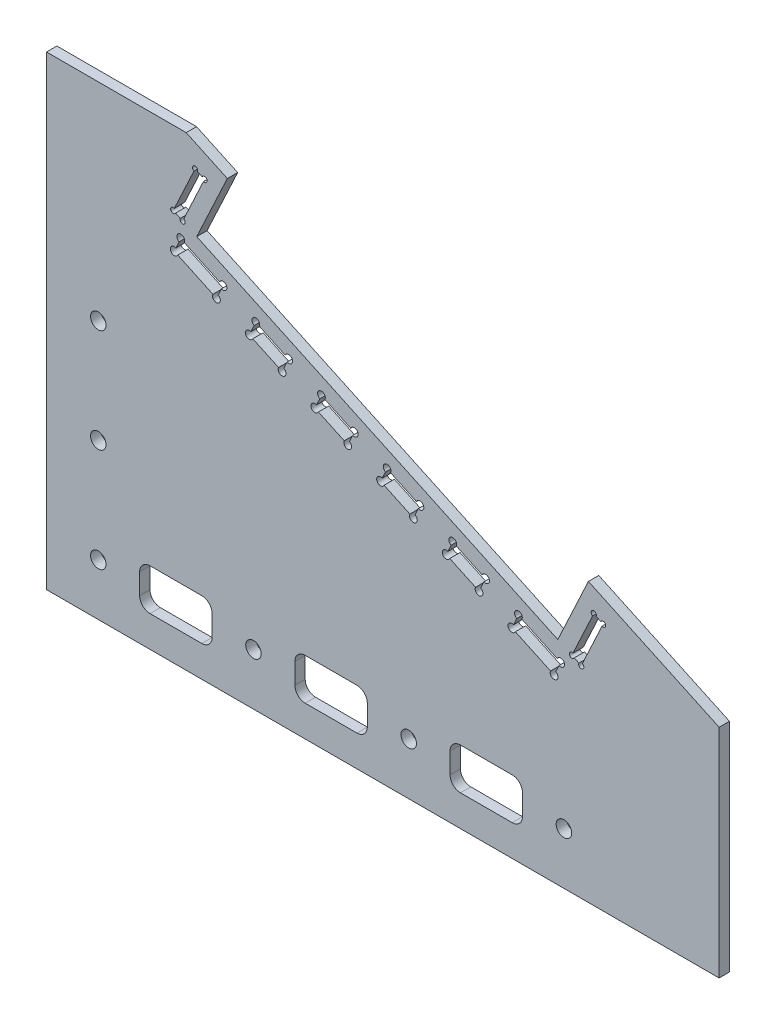
SolidWorks part; units mm, degrees
material "Thornel Mat VMA"
ref_plane "前视基准面" through (0, 0, 0) normal (0, 0, 1) x (1, 0, 0)
ref_plane "上视基准面" through (0, 0, 0) normal (0, 1, 0) x (1, 0, 0)
ref_plane "右视基准面" through (0, 0, 0) normal (1, 0, 0) x (0, 0, -1)
sketch "草图1" plane through (0, 0, 0) normal (0, 0, 1) x (1, 0, 0)
  line L1 (0, 0) -> (130, 0)
  line L2 (0, 0) -> (0, 90)
  line L3 (0, 90) -> (130, 90)
  line L4 (130, 0) -> (130, 90)
  circle A0 centre (10, 10) radius 1.5
  circle A1 centre (10, 30) radius 1.5
  circle A2 centre (10, 50) radius 1.5
  circle A3 centre (40, 10) radius 1.5
  circle A4 centre (70, 10) radius 1.5
  circle A5 centre (100, 10) radius 1.5
  dimension "D3" = 3
  dimension "D1" = 90
  dimension "D2" = 130
  dimension "D4" = 10
  dimension "D5" = 10
  dimension "D6" = 20
  dimension "D7" = 20
  dimension "D8" = 30
  dimension "D9" = 30
  dimension "D10" = 30
extrude "凸台-拉伸1" add sketch "草图1" along normal blind 2
sketch "草图2" plane through (0, 0, 2) normal (0, 0, 1) x (1, 0, 0)
  line L0 (27, 90) -> (130, 41.9703)
  line L1 (130, 90) -> (0, 90) construction
  line L2 (130, 0) -> (130, 90) construction
  line L3 (0, 90) -> (0, 0) construction
  line L4 (27, 90) -> (130, 90)
  line L5 (130, 90) -> (130, 41.9703)
  dimension "D1" = 27
  dimension "D2" = 25
extrude "切除-拉伸1" cut sketch "草图2" against normal through all
sketch "草图3" plane through (0, 0, 2) normal (0, 0, 1) x (1, 0, 0)
  line L0 (34.9483, 86.2936) -> (104.734, 53.752)
  line L1 (34.9483, 86.2936) -> (29.0317, 73.6053)
  line L2 (104.734, 53.752) -> (98.8174, 41.0637)
  line L3 (29.0317, 73.6053) -> (98.8174, 41.0637)
  line L4 (27, 90) -> (130, 41.9703) construction
  dimension "D1" = 14
  dimension "D2" = 77
  dimension "D3" = 8.77
extrude "切除-拉伸2" cut sketch "草图3" against normal through all
sketch "草图4" plane through (0, 0, 2) normal (0, 0, 1) x (1, 0, 0)
  line L0 (25.0449, 72.1543) -> (100.2684, 37.0769) construction
  line L1 (29.0317, 73.6053) -> (98.8174, 41.0637) construction
  line L2 (34.9483, 86.2936) -> (29.0317, 73.6053) construction
  line L3 (98.8174, 41.0637) -> (104.734, 53.752) construction
  line L4 (25.0449, 72.1543) -> (32.2294, 87.5615) construction
  line L5 (27, 90) -> (34.9483, 86.2936) construction
  line L6 (100.2684, 37.0769) -> (107.4529, 52.4842) construction
  line L7 (104.734, 53.752) -> (130, 41.9703) construction
  line L8 (30.5389, 83.9363) -> (26.3127, 74.8732)
  line L9 (30.5389, 83.9363) -> (28.7172, 84.7857)
  line L10 (26.3127, 74.8732) -> (24.4911, 75.7226)
  line L11 (28.7172, 84.7857) -> (24.4911, 75.7226)
  line L12 (105.7625, 48.8589) -> (101.5363, 39.7959)
  line L13 (105.7625, 48.8589) -> (107.5751, 48.0137)
  line L14 (101.5363, 39.7959) -> (103.3489, 38.9506)
  line L15 (107.5751, 48.0137) -> (103.3489, 38.9506)
  line L16 (25.9512, 71.7316) -> (34.108, 67.9281)
  line L17 (25.9512, 71.7316) -> (24.6833, 69.0127)
  line L18 (34.108, 67.9281) -> (32.8401, 65.2092)
  line L19 (24.6833, 69.0127) -> (32.8401, 65.2092)
  line L20 (40.4521, 64.9697) -> (46.7963, 62.0114)
  line L21 (40.4521, 64.9697) -> (39.1843, 62.2508)
  line L22 (46.7963, 62.0114) -> (45.5284, 59.2925)
  line L23 (39.1843, 62.2508) -> (45.5284, 59.2925)
  line L24 (78.517, 47.2198) -> (84.8612, 44.2615)
  line L25 (78.517, 47.2198) -> (77.2492, 44.5009)
  line L26 (84.8612, 44.2615) -> (83.5933, 41.5425)
  line L27 (77.2492, 44.5009) -> (83.5933, 41.5425)
  line L28 (91.2054, 41.3031) -> (99.3621, 37.4996)
  line L29 (91.2054, 41.3031) -> (89.9375, 38.5842)
  line L30 (99.3621, 37.4996) -> (98.0943, 34.7806)
  line L31 (89.9375, 38.5842) -> (98.0943, 34.7806)
  line L32 (53.1404, 59.0531) -> (59.4846, 56.0948)
  line L37 (53.1404, 59.0531) -> (51.8726, 56.3342)
  line L38 (59.4846, 56.0948) -> (58.2167, 53.3758)
  line L39 (51.8726, 56.3342) -> (58.2167, 53.3758)
  line L40 (65.8287, 53.1364) -> (72.1729, 50.1781)
  line L41 (65.8287, 53.1364) -> (64.5609, 50.4175)
  line L42 (72.1729, 50.1781) -> (70.905, 47.4592)
  line L43 (64.5609, 50.4175) -> (70.905, 47.4592)
  point P21 (25.3173, 70.3722)
  point P37 (33.474, 66.5686)
  dimension "D1" = 3
  dimension "D2" = 3
  dimension "D3" = 3
  dimension "D4" = 1
  dimension "D5" = 2
  dimension "D6" = 9
  dimension "D7" = 9
  dimension "D8" = 1.5
  dimension "D9" = 7
  dimension "D10" = 7
  dimension "D11" = 7
  dimension "D12" = 7
  dimension "D13" = 1
  dimension "D14" = 3
  dimension "D15" = 3
  dimension "D16" = 3
  dimension "D17" = 3
  dimension "D18" = 10
  dimension "D19" = 2.01
  dimension "D20" = 3
  dimension "D21" = 10
  dimension "D22" = 7
  dimension "D23" = 7
  dimension "D24" = 3
  dimension "D25" = 7
  dimension "D26" = 7
  dimension "D27" = 3
extrude "切除-拉伸3" cut sketch "草图4" against normal through all
sketch "草图5" plane through (0, 0, 2) normal (0, 0, 1) x (1, 0, 0)
  line L0 (114.7802, 44.6539) -> (110.554, 35.5908)
  line L1 (114.7802, 44.6539) -> (117.4992, 43.386)
  line L2 (110.554, 35.5908) -> (113.273, 34.323)
  line L3 (117.4992, 43.386) -> (113.273, 34.323)
  line L4 (101.5363, 39.7959) -> (103.3489, 38.9506) construction
  line L5 (103.3489, 38.9506) -> (107.5751, 48.0137) construction
  dimension "D1" = 7.95
  dimension "D2" = 3
  dimension "D3" = 10
extrude "切除-拉伸4" [suppressed] cut sketch "草图5" against normal through all
sketch "草图6" plane through (0, 0, 2) normal (0, 0, 1) x (1, 0, 0)
  circle A0 centre (24.6833, 69.0127) radius 0.75
  circle A1 centre (25.9512, 71.7316) radius 0.75
  circle A2 centre (34.108, 67.9281) radius 0.75
  circle A3 centre (32.8401, 65.2092) radius 0.75
  circle A4 centre (45.5284, 59.2925) radius 0.75
  circle A5 centre (39.1843, 62.2508) radius 0.75
  circle A6 centre (40.4521, 64.9697) radius 0.75
  circle A7 centre (46.7963, 62.0114) radius 0.75
  circle A8 centre (78.517, 47.2198) radius 0.75
  circle A9 centre (77.2492, 44.5009) radius 0.75
  circle A10 centre (83.5933, 41.5425) radius 0.75
  circle A11 centre (84.8612, 44.2615) radius 0.75
  circle A12 centre (98.0943, 34.7806) radius 0.75
  circle A13 centre (99.3621, 37.4996) radius 0.75
  circle A14 centre (91.2054, 41.3031) radius 0.75
  circle A15 centre (89.9375, 38.5842) radius 0.75
  circle A16 centre (26.3127, 74.8732) radius 0.5
  circle A17 centre (24.4911, 75.7226) radius 0.5
  circle A18 centre (28.7172, 84.7857) radius 0.5
  circle A19 centre (30.5389, 83.9363) radius 0.5
  circle A20 centre (103.3489, 38.9506) radius 0.5
  circle A21 centre (101.5363, 39.7959) radius 0.5
  circle A22 centre (105.7625, 48.8589) radius 0.5
  circle A23 centre (107.5751, 48.0137) radius 0.5
  circle A24 centre (53.1404, 59.0531) radius 0.75
  circle A25 centre (59.4846, 56.0948) radius 0.75
  circle A26 centre (51.8726, 56.3342) radius 0.75
  circle A27 centre (58.2167, 53.3758) radius 0.75
  circle A28 centre (65.8287, 53.1364) radius 0.75
  circle A29 centre (72.1729, 50.1781) radius 0.75
  circle A30 centre (70.905, 47.4592) radius 0.75
  circle A31 centre (64.5609, 50.4175) radius 0.75
  dimension "D1" = 1
  dimension "D2" = 1.5
  dimension "D3" = 1.5
  dimension "D4" = 1.5
  dimension "D5" = 1.5
  dimension "D6" = 1.5
  dimension "D7" = 1.5
  dimension "D8" = 1.5
  dimension "D9" = 1.5
  dimension "D10" = 1.5
extrude "切除-拉伸5" cut sketch "草图6" against normal blind 10
sketch "草图7" plane through (0, 0, 2) normal (0, 0, 1) x (1, 0, 0)
  line L0 (0, 20) -> (130, 20) construction
  line L1 (0, 90) -> (0, 0) construction
  line L2 (130, 0) -> (130, 41.9703) construction
  line L3 (0, 0) -> (130, 0) construction
  line L4 (130, 20) -> (112.6424, 50.0643)
  line L5 (104.734, 53.752) -> (130, 41.9703) construction
  line L6 (112.6424, 50.0643) -> (130, 41.9703)
  line L7 (130, 41.9703) -> (130, 20)
  dimension "D1" = 20
  dimension "D2" = 60
extrude "切除-拉伸6" [suppressed] cut sketch "草图7" against normal blind 10
fillet "圆角1" [suppressed] radius 2
sketch "草图8" plane through (0, 0, 0) normal (0, 0, -1) x (-1, 0, 0)
  line L0 (-90, 14) -> (-80, 14) construction
  line L1 (-92, 8) -> (-92, 12) construction
  line L2 (-80, 6) -> (-90, 6) construction
  line L3 (-78, 12) -> (-78, 8) construction
  line L4 (-62, 8) -> (-62, 12) construction
  line L5 (-50, 6) -> (-60, 6) construction
  line L6 (-60, 14) -> (-50, 14) construction
  line L7 (-48, 12) -> (-48, 8) construction
  line L8 (-30, 14) -> (-20, 14) construction
  line L9 (-32, 8) -> (-32, 12) construction
  line L10 (-20, 6) -> (-30, 6) construction
  line L11 (-18, 12) -> (-18, 8) construction
  line L12 (-90, 14) -> (-80, 14)
  line L13 (-92, 8) -> (-92, 12)
  line L14 (-80, 6) -> (-90, 6)
  line L15 (-78, 12) -> (-78, 8)
  line L16 (-62, 8) -> (-62, 12)
  line L17 (-50, 6) -> (-60, 6)
  line L18 (-60, 14) -> (-50, 14)
  line L19 (-48, 12) -> (-48, 8)
  line L20 (-30, 14) -> (-20, 14)
  line L21 (-32, 8) -> (-32, 12)
  line L22 (-20, 6) -> (-30, 6)
  line L23 (-18, 12) -> (-18, 8)
  arc A0 (-78, 12) -> (-80, 14) centre (-80, 12) ccw construction
  arc A1 (-90, 14) -> (-92, 12) centre (-90, 12) ccw construction
  arc A2 (-92, 8) -> (-90, 6) centre (-90, 8) ccw construction
  arc A3 (-80, 6) -> (-78, 8) centre (-80, 8) ccw construction
  arc A4 (-60, 14) -> (-62, 12) centre (-60, 12) ccw construction
  arc A5 (-62, 8) -> (-60, 6) centre (-60, 8) ccw construction
  arc A6 (-48, 12) -> (-50, 14) centre (-50, 12) ccw construction
  arc A7 (-50, 6) -> (-48, 8) centre (-50, 8) ccw construction
  arc A8 (-30, 14) -> (-32, 12) centre (-30, 12) ccw construction
  arc A9 (-32, 8) -> (-30, 6) centre (-30, 8) ccw construction
  arc A10 (-18, 12) -> (-20, 14) centre (-20, 12) ccw construction
  arc A11 (-20, 6) -> (-18, 8) centre (-20, 8) ccw construction
  arc A12 (-78, 12) -> (-80, 14) centre (-80, 12) ccw
  arc A13 (-90, 14) -> (-92, 12) centre (-90, 12) ccw
  arc A14 (-92, 8) -> (-90, 6) centre (-90, 8) ccw
  arc A15 (-80, 6) -> (-78, 8) centre (-80, 8) ccw
  arc A16 (-60, 14) -> (-62, 12) centre (-60, 12) ccw
  arc A17 (-62, 8) -> (-60, 6) centre (-60, 8) ccw
  arc A18 (-48, 12) -> (-50, 14) centre (-50, 12) ccw
  arc A19 (-50, 6) -> (-48, 8) centre (-50, 8) ccw
  arc A20 (-30, 14) -> (-32, 12) centre (-30, 12) ccw
  arc A21 (-32, 8) -> (-30, 6) centre (-30, 8) ccw
  arc A22 (-18, 12) -> (-20, 14) centre (-20, 12) ccw
  arc A23 (-20, 6) -> (-18, 8) centre (-20, 8) ccw
extrude "切除-拉伸7" cut sketch "草图8" against normal through all
